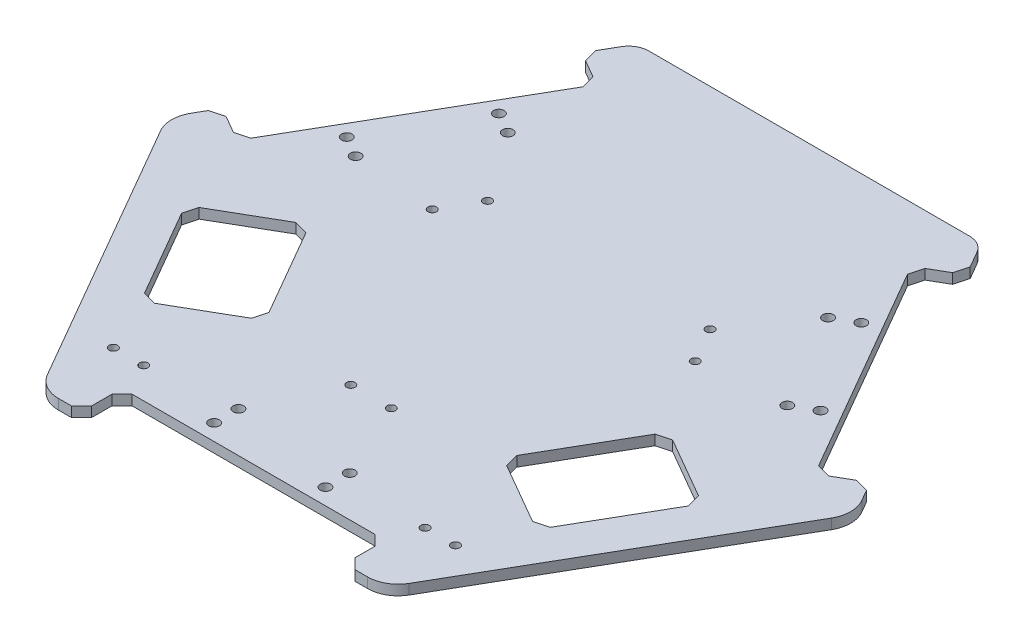
SolidWorks part; units mm, degrees
material "5052-H32"
ref_plane "前基準面" through (0, 0, 0) normal (0, 0, 1) x (1, 0, 0)
ref_plane "上基準面" through (0, 0, 0) normal (0, 1, 0) x (1, 0, 0)
ref_plane "右基準面" through (0, 0, 0) normal (1, 0, 0) x (0, 0, -1)
sketch "草圖1" plane through (0, 0, 0) normal (0, 1, 0) x (1, 0, 0)
  line L1 (85, 147.2243) -> (-85, 147.2243)
  line L2 (-85, 147.2243) -> (-170, 0)
  line L3 (-170, 0) -> (-85, -147.2243)
  line L4 (-85, -147.2243) -> (85, -147.2243)
  line L5 (85, -147.2243) -> (170, 0)
  line L6 (170, 0) -> (85, 147.2243)
  circle A0 centre (0, 0) radius 147.2243 construction
  dimension "D1" = 170
extrude "填料-伸長1" add sketch "草圖1" along normal blind 5
ref_axis "基準軸1" through (0, 5.25, 0) along (0, -1, 0)
sketch "草圖16" plane through (0, 5, 0) normal (0, 1, 0) x (1, 0, 0)
  line L0 (-65, -147.2243) -> (65, -147.2243)
  line L1 (-65, -147.2243) -> (-65, -127.2243)
  line L2 (65, -147.2243) -> (65, -127.2243)
  line L3 (-65, -127.2243) -> (65, -127.2243)
  line L4 (-85, -147.2243) -> (85, -147.2243) construction
  point P6 (0, -147.2243)
  point P7 (0, -147.2243)
  dimension "D1" = 20
  dimension "D2" = 130
extrude "除料-伸長16" cut sketch "草圖16" against normal blind 10
sketch "草圖9" plane through (0, 5, 0) normal (0, 1, 0) x (1, 0, 0)
  line L0 (-27.5, -107.2243) -> (27.5, -107.2243) construction
  line L1 (27.5, -107.2243) -> (27.5, -119.2243) construction
  line L2 (-27.5, -107.2243) -> (-27.5, -119.2243) construction
  line L3 (-27.5, -119.2243) -> (27.5, -119.2243) construction
  line L4 (65, -127.2243) -> (-65, -127.2243) construction
  circle A0 centre (-27.5, -119.2243) radius 2.6
  circle A1 centre (-27.5, -107.2243) radius 2.6
  circle A2 centre (27.5, -107.2243) radius 2.6
  circle A3 centre (27.5, -119.2243) radius 2.6
  point P11 (0, -119.2243)
  point P12 (0, -127.2243)
  dimension "D1" = 5.2
  dimension "D2" = 12
  dimension "D3" = 8
  dimension "D4" = 55
extrude "除料-伸長8" cut sketch "草圖9" against normal through all and the other way through all
sketch "草圖18" plane through (0, 5, 0) normal (0, 1, 0) x (1, 0, 0)
  line L0 (-10, -69.2243) -> (10, -69.2243) construction
  line L1 (65, -127.2243) -> (-65, -127.2243) construction
  circle A0 centre (-10, -69.2243) radius 2.1
  circle A1 centre (10, -69.2243) radius 2.1
  point P4 (0, -69.2243)
  point P7 (0, -127.2243)
  dimension "D3" = 4.2
  dimension "D4" = 4.2
  dimension "D1" = 20
  dimension "D2" = 58
extrude "除料-伸長17" cut sketch "草圖18" against normal up to next
pattern_circular "環狀複製排列1" count 3 over 360 about axis through (0, 5.25, 0) along (0, -1, 0) of "除料-伸長8", "除料-伸長16", "除料-伸長17"
chamfer "導角4" distance 5 angle 45 12 edges at (65, 2.5, 127.2243) (65, 2.5, 147.2243) (-65, 2.5, 147.2243) (-65, 2.5, 127.2243) (77.6795, 2.5, -119.9038) (95, 2.5, -129.9038) (160, 2.5, -17.3205) (142.6795, 2.5, -7.3205) (-142.6795, 2.5, -7.3205) (-160, 2.5, -17.3205) (-95, 2.5, -129.9038) (-77.6795, 2.5, -119.9038)
sketch "草圖5" plane through (0, 5, 0) normal (0, 1, 0) x (1, 0, 0)
  line L0 (0, 0) -> (0, -112) construction
  line L1 (0, -112) -> (-77, -112) construction
  line L2 (-84.5, -112) -> (-69.5, -112) construction
  circle A0 centre (-84.5, -112) radius 2.1
  circle A1 centre (-69.5, -112) radius 2.1
  circle A2 centre (84.5, -112) radius 2.1
  circle A3 centre (69.5, -112) radius 2.1
  point P8 (-77, -112)
  dimension "D1" = 4.2
  dimension "D2" = 15
  dimension "D3" = 112
  dimension "D4" = 77
extrude "除料-伸長5" cut sketch "草圖5" against normal through all
sketch "草圖8" plane through (0, 5, 0) normal (0, 1, 0) x (1, 0, 0)
  line L0 (-127.6795, -33.3013) -> (-97.6795, -85.2628)
  line L1 (-127.6795, -33.3013) -> (-88.7083, -10.8013)
  line L2 (-97.6795, -85.2628) -> (-58.7083, -62.7628)
  line L3 (-88.7083, -10.8013) -> (-58.7083, -62.7628)
  line L5 (-170, 0) -> (-85, -147.2243) construction
  line L6 (-170, 0) -> (-145, -43.3013) construction
  line L7 (-145, -43.3013) -> (-127.6795, -33.3013) construction
  dimension "D1" = 45
  dimension "D2" = 60
  dimension "D3" = 20
  dimension "D4" = 50
extrude "除料-伸長7" cut sketch "草圖8" against normal through all
chamfer "導角2" distance 5 angle 45 4 edges at (-58.7083, 2.5, 62.7628) (-97.6795, 2.5, 85.2628) (-127.6795, 2.5, 33.3013) (-88.7083, 2.5, 10.8013)
mirror "鏡射1" about plane through (0, 0, 0) normal (1, 0, 0) of "除料-伸長7", "導角2"
fillet "圓角2" radius 15 4 edges at (-170, 2.5, 0) (-85, 2.5, 147.2243) (85, 2.5, 147.2243) (170, 2.5, 0)
fillet "圓角3" radius 10 2 edges at (85, 2.5, -147.2243) (-85, 2.5, -147.2243)
